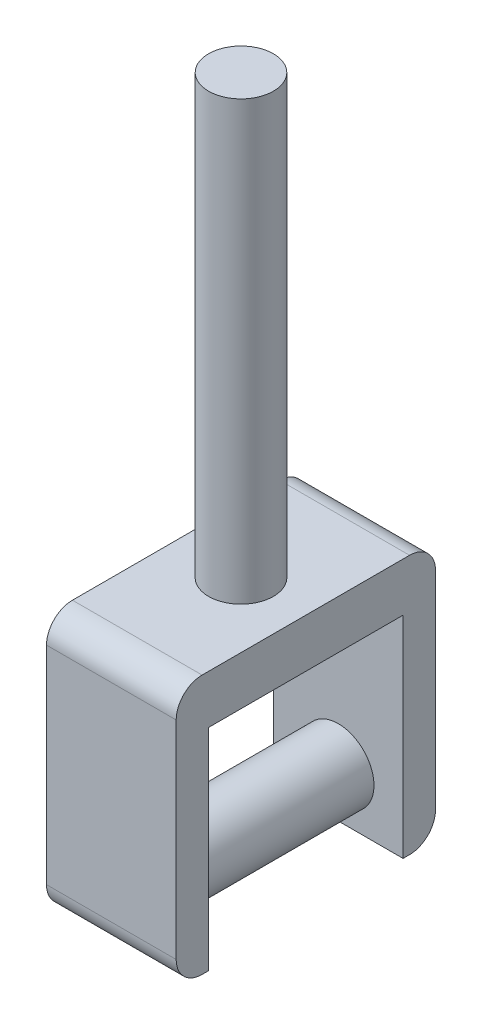
SolidWorks part; units mm, degrees
ref_plane "前视基准面" through (0, 0, 0) normal (0, 0, 1) x (1, 0, 0)
ref_plane "上视基准面" through (0, 0, 0) normal (0, 1, 0) x (1, 0, 0)
ref_plane "右视基准面" through (0, 0, 0) normal (1, 0, 0) x (0, 0, -1)
sketch "草图1" plane through (0, 0, 0) normal (0, 1, 0) x (1, 0, 0)
  circle A0 centre (0, 0) radius 10
  dimension "D1" = 20
extrude "凸台-拉伸1" add sketch "草图1" along normal blind 150
sketch "草图2" plane through (0, 0, 0) normal (1, 0, 0) x (0, 0, -1)
  line L0 (-30, -65) -> (-30, 0)
  line L1 (-32, 15) -> (32, 15)
  line L2 (-40, 7) -> (-40, -57)
  line L3 (-32, -65) -> (-30, -65)
  line L4 (40, 7) -> (40, -57)
  line L5 (-30, 0) -> (30, 0)
  line L6 (30, 0) -> (30, -65)
  line L7 (30, -65) -> (32, -65)
  line L8 (-10, 0) -> (10, 0) construction
  arc A0 (-40, 7) -> (-32, 15) centre (-32, 7) cw
  arc A1 (40, 7) -> (32, 15) centre (32, 7) ccw
  arc A2 (40, -57) -> (32, -65) centre (32, -57) cw
  arc A3 (-32, -65) -> (-40, -57) centre (-32, -57) cw
  dimension "D7" = 8
  dimension "D1" = 15
  dimension "D2" = 60
  dimension "D3" = 80
  dimension "D4" = 40
  dimension "D5" = 30
  dimension "D6" = 65
extrude "凸台-拉伸2" add sketch "草图2" along normal blind 20 and the other way blind 20
sketch "草图3" plane through (0, 0, -30) normal (0, 0, 1) x (1, 0, 0)
  line L1 (-20, 0) -> (20, 0) construction
  circle A0 centre (0, -50) radius 11.0248
  point P2 (0, 0)
  point P4 (0, 0)
  dimension "D1" = 50
extrude "凸台-拉伸3" add sketch "草图3" along normal up to next
